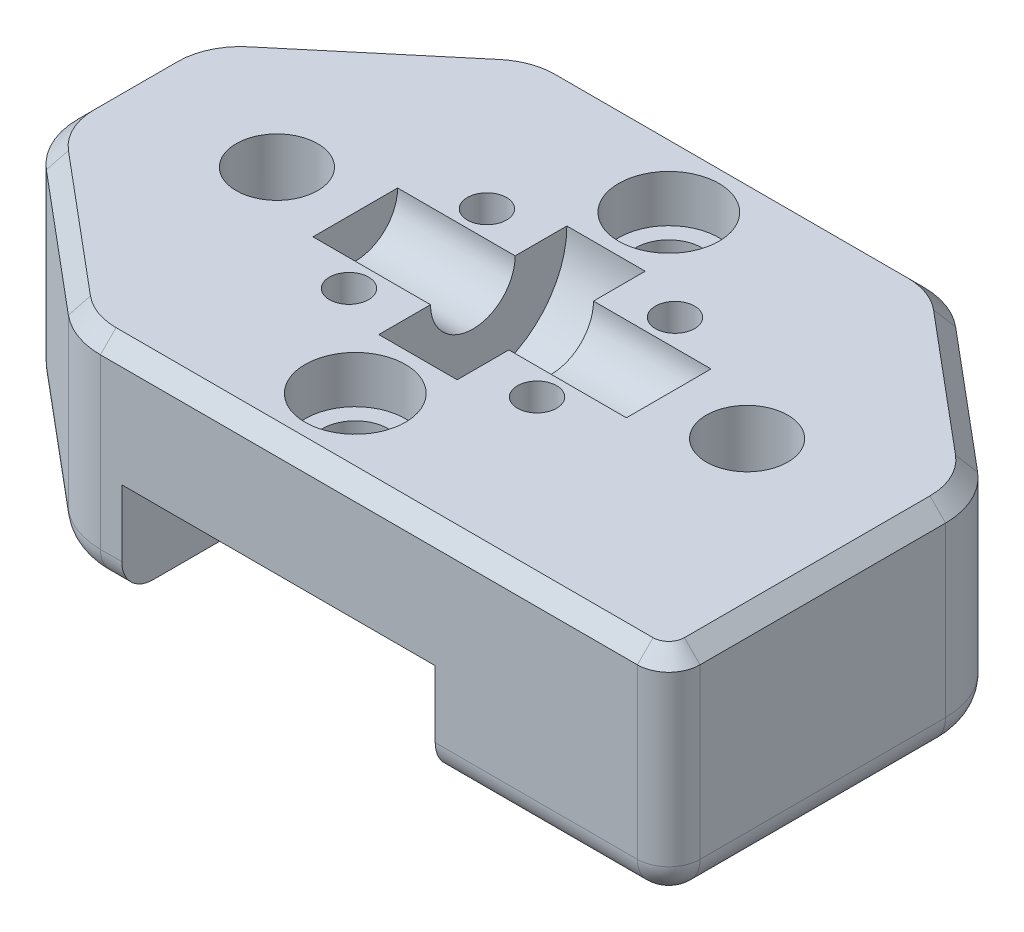
SolidWorks part; units mm, degrees
ref_plane "Front Plane" through (0, 0, 0) normal (0, 0, 1) x (1, 0, 0)
ref_plane "Top Plane" through (0, 0, 0) normal (0, 1, 0) x (1, 0, 0)
ref_plane "Right Plane" through (0, 0, 0) normal (1, 0, 0) x (0, 0, -1)
sketch "Sketch1" plane through (0, 0, 0) normal (0, 1, 0) x (1, 0, 0)
  line L0 (14.3035, 0) -> (-14.3035, 0)
  line L1 (-18.3852, 1.4856) -> (-29.4817, 10.7967)
  line L2 (-31.75, 15.6611) -> (-31.75, 22.4389)
  line L3 (-31.75, 19.05) -> (0, 19.05) construction
  line L4 (0, 19.05) -> (0, 0) construction
  line L6 (31.75, 15.6611) -> (31.75, 22.4389)
  line L7 (-18.3852, 36.6144) -> (-29.4817, 27.3033)
  line L8 (14.3035, 38.1) -> (-14.3035, 38.1)
  line L9 (18.3852, 36.6144) -> (29.4817, 27.3033)
  line L10 (14.3035, 0) -> (29.21, 0)
  line L11 (31.75, 2.54) -> (31.75, 15.6611)
  arc A0 (-29.4817, 10.7967) -> (-31.75, 15.6611) centre (-25.4, 15.6611) cw
  arc A1 (-18.3852, 1.4856) -> (-14.3035, 0) centre (-14.3035, 6.35) ccw
  arc A4 (-29.4817, 27.3033) -> (-31.75, 22.4389) centre (-25.4, 22.4389) ccw
  arc A5 (-18.3852, 36.6144) -> (-14.3035, 38.1) centre (-14.3035, 31.75) cw
  arc A6 (18.3852, 36.6144) -> (14.3035, 38.1) centre (14.3035, 31.75) ccw
  arc A7 (29.4817, 27.3033) -> (31.75, 22.4389) centre (25.4, 22.4389) cw
  arc A8 (29.21, 0) -> (31.75, 2.54) centre (29.21, 2.54) ccw
  point P9 (-31.75, 12.7)
  point P31 (31.75, 19.05)
  dimension "D5" = 6.35
  dimension "D6" = 6.35
  dimension "D7" = 2.54
  dimension "D1" = 19.05
  dimension "D2" = 6.35
  dimension "D3" = 31.75
  dimension "D4" = 140
extrude "Boss-Extrude2" add sketch "Sketch1" along normal blind 17.4625
sketch "Sketch2" plane through (0, 17.4625, 0) normal (0, 1, 0) x (1, 0, 0)
  line L0 (-14.3035, 0) -> (29.21, 0) construction
  line L2 (14.3035, 38.1) -> (-14.3035, 38.1) construction
  line L3 (0, 38.1) -> (0, 0) construction
  circle A0 centre (-19.05, 19.05) radius 3.302
  circle A3 centre (19.05, 19.05) radius 3.302
  circle A8 centre (7.62, 24.638) radius 1.5875
  circle A9 centre (7.62, 13.462) radius 1.5875
  circle A10 centre (-7.62, 13.462) radius 1.5875
  circle A11 centre (-7.62, 24.638) radius 1.5875
  circle A12 centre (0, 31.75) radius 2.667
  circle A13 centre (0, 6.35) radius 2.667
  dimension "D2" = 6.604
  dimension "D7" = 7.62
  dimension "D8" = 3.175
  dimension "D10" = 5.588
  dimension "D4" = 5.334
  dimension "D3" = 19.05
  dimension "D5" = 6.35
  dimension "D6" = 6.35
  dimension "D9" = 5.588
  dimension "D11" = 7.62
  dimension "D12" = 25.4
  dimension "D13" = 19.05
extrude "Cut-Extrude1" cut sketch "Sketch2" against normal through all
sketch "Sketch3" plane through (-31.75, 0, 0) normal (-1, 0, 0) x (0, 0, 1)
  line L0 (-22.4389, 17.4625) -> (-15.6611, 17.4625) construction
  circle A0 centre (-19.05, 17.4625) radius 3.429
  dimension "D1" = 6.858
extrude "Cut-Extrude3" cut sketch "Sketch3" against normal blind 25.4 from offset 19.05 offset against normal yes
sketch "Sketch4" plane through (-31.75, 0, 0) normal (-1, 0, 0) x (0, 0, 1)
  line L0 (-22.4389, 17.4625) -> (-15.6611, 17.4625) construction
  line L1 (-26.67, 17.4625) -> (-11.43, 17.4625)
  arc A0 (-26.67, 17.4625) -> (-11.43, 17.4625) centre (-19.05, 17.4625) ccw
  dimension "D1" = 7.62
extrude "Cut-Extrude4" cut sketch "Sketch4" against normal blind 6.35 from offset 28.575 offset against normal yes
sketch "Sketch5" plane through (0, 0, -38.1) normal (0, 0, -1) x (-1, 0, 0)
  line L0 (-14.3035, 0) -> (14.3035, 0) construction
  line L1 (12.573, 0) -> (-12.827, 0)
  line L2 (12.573, 0) -> (12.573, 7.9375)
  line L3 (12.573, 7.9375) -> (-12.827, 7.9375)
  line L4 (-12.827, 0) -> (-12.827, 7.9375)
  line L5 (-14.3035, 17.4625) -> (14.3035, 17.4625) construction
  point P10 (0, 17.4625)
  dimension "D1" = 25.4
  dimension "D2" = 7.9375
  dimension "D3" = 12.827
extrude "Cut-Extrude5" cut sketch "Sketch5" against normal through all
sketch "Sketch6" plane through (0, 0, 0) normal (0, -1, 0) x (1, 0, 0)
  line L1 (13.208, -22.4229) -> (19.05, -25.7958)
  line L2 (19.05, -25.7958) -> (24.892, -22.4229)
  line L3 (24.892, -22.4229) -> (24.892, -15.6771)
  line L4 (24.892, -15.6771) -> (19.05, -12.3042)
  line L5 (19.05, -12.3042) -> (13.208, -15.6771)
  line L6 (13.208, -15.6771) -> (13.208, -22.4229)
  line L7 (-19.05, -25.7958) -> (-13.208, -22.4229)
  line L8 (-13.208, -22.4229) -> (-13.208, -15.6771)
  line L9 (-13.208, -15.6771) -> (-19.05, -12.3042)
  line L10 (-19.05, -12.3042) -> (-24.892, -15.6771)
  line L11 (-24.892, -15.6771) -> (-24.892, -22.4229)
  line L12 (-24.892, -22.4229) -> (-19.05, -25.7958)
  circle A0 centre (19.05, -19.05) radius 5.842 construction
  circle A1 centre (-19.05, -19.05) radius 5.842 construction
  dimension "D1" = 11.684
extrude "Cut-Extrude6" cut sketch "Sketch6" against normal blind 7.9375
sketch "Sketch9" plane through (0, 7.9375, 0) normal (0, -1, 0) x (1, 0, 0)
  line L0 (9.2075, -13.462) -> (9.2075, -24.638)
  line L1 (6.0325, -13.462) -> (6.0325, -24.638)
  line L2 (-6.0325, -24.638) -> (-6.0325, -13.462)
  line L3 (-9.2075, -24.638) -> (-9.2075, -13.462)
  circle A0 centre (7.62, -13.462) radius 1.5875 construction
  circle A1 centre (7.62, -24.638) radius 1.5875 construction
  circle A2 centre (-7.62, -24.638) radius 1.5875 construction
  circle A3 centre (-7.62, -13.462) radius 1.5875 construction
  arc A4 (9.2075, -24.638) -> (6.0325, -24.638) centre (7.62, -24.638) cw
  arc A5 (-6.0325, -24.638) -> (-9.2075, -24.638) centre (-7.62, -24.638) cw
  arc A6 (-9.2075, -13.462) -> (-6.0325, -13.462) centre (-7.62, -13.462) cw
  arc A7 (6.0325, -13.462) -> (9.2075, -13.462) centre (7.62, -13.462) cw
extrude "Cut-Extrude9" cut sketch "Sketch9" against normal blind 3.175
chamfer "Chamfer2" distance 2.54 angle 45 4 edges at (-7.62, 11.1125, -15.0495) (-7.62, 11.1125, -23.0505) (7.62, 11.1125, -15.0495) (7.62, 11.1125, -23.0505)
sketch "Sketch10" plane through (0, 17.4625, 0) normal (0, 1, 0) x (1, 0, 0)
  circle A0 centre (0, 6.35) radius 4.064
  circle A1 centre (0, 31.7584) radius 4.064
  dimension "D1" = 8.128
extrude "Cut-Extrude10" cut sketch "Sketch10" against normal blind 3.81
fillet "Fillet1" radius 2.54 16 edges at (-31.1551, 0, -25.1226) (-31.75, 0, -19.05) (-31.1551, 0, -12.9774) (-23.9335, 0, -6.1411) (-16.4753, 0, -0.383) (-13.4383, 0, 0) (-23.9335, 0, -31.9589) (-16.4753, 0, -37.717) (-13.4383, 0, -38.1) (21.0185, 0, 0) (31.75, 0, -12.4895) (31.1551, 0, -25.1226) (23.9335, 0, -31.9589) (16.4753, 0, -37.717) (13.5653, 0, -38.1) (31.0061, 0, -0.7439)
fillet "Fillet2" radius 1.27 8 edges at (-7.62, 7.9375, -26.2255) (-9.2075, 7.9375, -19.05) (-7.62, 7.9375, -11.8745) (-6.0325, 7.9375, -19.05) (7.62, 7.9375, -11.8745) (9.2075, 7.9375, -19.05) (7.62, 7.9375, -26.2255) (6.0325, 7.9375, -19.05)
chamfer "Chamfer3" distance 1.27 angle 45 14 edges at (16.4753, 17.4625, -37.717) (0, 17.4625, -38.1) (-16.4753, 17.4625, -37.717) (-23.9335, 17.4625, -31.9589) (-31.1551, 17.4625, -25.1226) (-31.75, 17.4625, -19.05) (-31.1551, 17.4625, -12.9774) (-23.9335, 17.4625, -6.1411) (-16.4753, 17.4625, -0.383) (7.4532, 17.4625, 0) (31.75, 17.4625, -12.4895) (31.1551, 17.4625, -25.1226) (23.9335, 17.4625, -31.9589) (31.0061, 17.4625, -0.7439)
